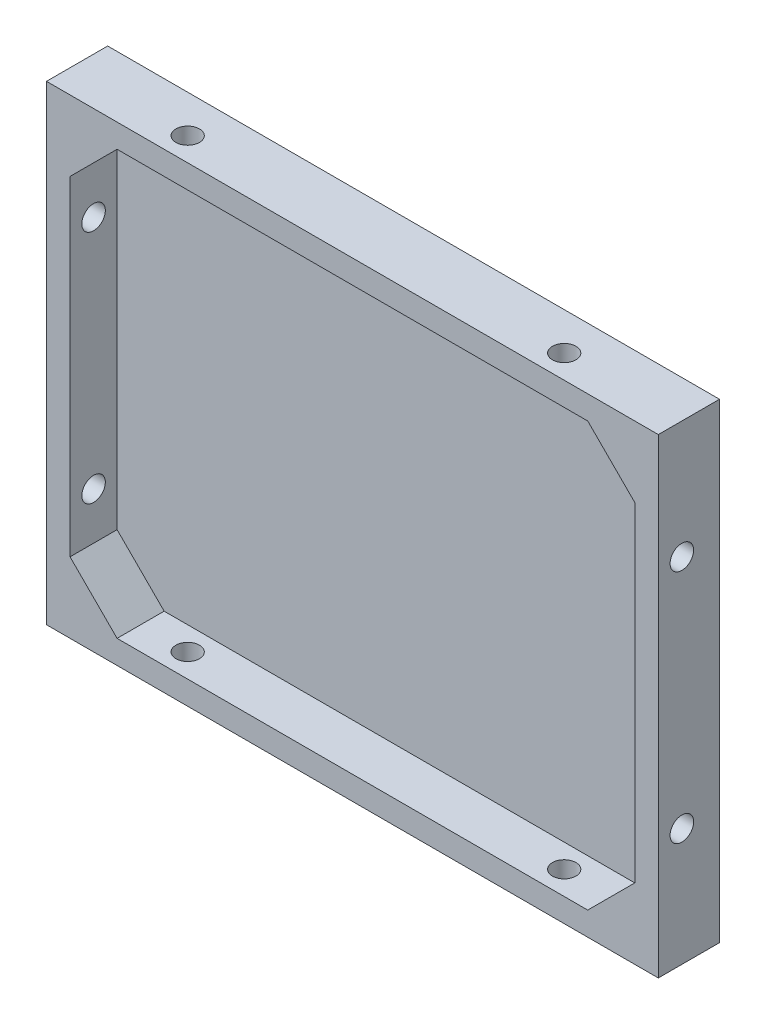
SolidWorks part; units mm, degrees
ref_plane "Plan de face" through (0, 0, 0) normal (0, 0, 1) x (1, 0, 0)
ref_plane "Plan de dessus" through (0, 0, 0) normal (0, 1, 0) x (1, 0, 0)
ref_plane "Plan de droite" through (0, 0, 0) normal (1, 0, 0) x (0, 0, -1)
sketch "Esquisse1" plane through (0, 0, 0) normal (0, 0, 1) x (1, 0, 0)
  line L0 (44.1184, 33.7284) -> (54.1184, 33.7284)
  line L1 (-75.8816, 33.7284) -> (44.1184, 33.7284)
  line L2 (-75.8816, 33.7284) -> (-75.8816, -66.2716)
  line L3 (-75.8816, -66.2716) -> (54.1184, -66.2716)
  line L4 (54.1184, 23.7284) -> (54.1184, -66.2716)
  line L5 (54.1184, 33.7284) -> (54.1184, 23.7284)
  point P6 (54.1184, 33.7284)
  dimension "D1" = 130
  dimension "D2" = 100
extrude "Boss.-Extru.1" add sketch "Esquisse1" along normal blind 13
shell "Coque1" thickness 5 removed face at (-10.8816, -16.2716, 13)
sketch "Esquisse2" plane through (-75.8816, 0, 0) normal (-1, 0, 0) x (0, 0, 1)
  line L0 (13, 33.7284) -> (13, -66.2716) construction
  line L1 (13, 33.7284) -> (0, 33.7284) construction
  line L2 (13, -66.2716) -> (0, -66.2716) construction
  circle A0 centre (8, 8.7284) radius 2.5
  circle A1 centre (8, -41.2716) radius 2.5
  dimension "D1" = 5
  dimension "D2" = 5
  dimension "D3" = 5
  dimension "D4" = 5
  dimension "D5" = 25
  dimension "D6" = 25
extrude "Enlèv. mat.-Extru.1" cut sketch "Esquisse2" against normal up to surface (130 mm away) contours A1 | A0 region at (-75.8816, -41.2716, 8) up to face at (54.1184, -16.2716, 6.5)
sketch "Esquisse3" plane through (0, -66.2716, 0) normal (0, -1, 0) x (1, 0, 0)
  line L0 (-75.8816, 13) -> (54.1184, 13) construction
  line L2 (54.1184, 13) -> (54.1184, 0) construction
  line L3 (-75.8816, 13) -> (-75.8816, 0) construction
  circle A0 centre (-50.8816, 8) radius 2.5
  circle A1 centre (29.1184, 8) radius 2.5
  dimension "D1" = 5
  dimension "D2" = 5
  dimension "D3" = 5
  dimension "D4" = 5
  dimension "D5" = 25
  dimension "D6" = 25
extrude "Enlèv. mat.-Extru.2" cut sketch "Esquisse3" against normal up to surface (100 mm away) up to face at (-10.8816, 33.7284, 6.5)
sketch "Esquisse4" plane through (0, 0, 3) normal (0, 0, 1) x (1, 0, 0)
  line L0 (-60.8816, 28.7284) -> (-70.8816, 18.7284)
  line L1 (49.1184, 28.7284) -> (-70.8816, 28.7284) construction
  line L2 (-70.8816, 28.7284) -> (-70.8816, -61.2716) construction
  line L3 (-70.8816, 18.7284) -> (-70.8816, 28.7284)
  line L4 (-70.8816, 28.7284) -> (-60.8816, 28.7284)
  line L5 (49.1184, 28.7284) -> (49.1184, 18.7284)
  line L6 (49.1184, -61.2716) -> (49.1184, 28.7284) construction
  line L7 (49.1184, 18.7284) -> (39.1184, 28.7284)
  line L8 (39.1184, 28.7284) -> (49.1184, 28.7284)
  line L9 (49.1184, 28.7284) -> (-70.8816, 28.7284) construction
  line L10 (49.1184, -61.2716) -> (49.1184, -51.2716)
  line L11 (49.1184, -51.2716) -> (39.1184, -61.2716)
  line L12 (-70.8816, -61.2716) -> (49.1184, -61.2716) construction
  line L13 (39.1184, -61.2716) -> (49.1184, -61.2716)
  line L14 (-60.8816, -61.2716) -> (-70.8816, -51.2716)
  line L15 (-70.8816, 28.7284) -> (-70.8816, -61.2716) construction
  line L16 (-70.8816, -51.2716) -> (-70.8816, -61.2716)
  line L17 (-70.8816, -61.2716) -> (-60.8816, -61.2716)
  dimension "D1" = 10
  dimension "D2" = 10
  dimension "D3" = 10
  dimension "D4" = 10
  dimension "D5" = 10
  dimension "D6" = 10
  dimension "D7" = 10
  dimension "D8" = 10
extrude "Boss.-Extru.2" add sketch "Esquisse4" along normal up to surface (10 mm away) up to face at (-10.8816, -16.2716, 13)
